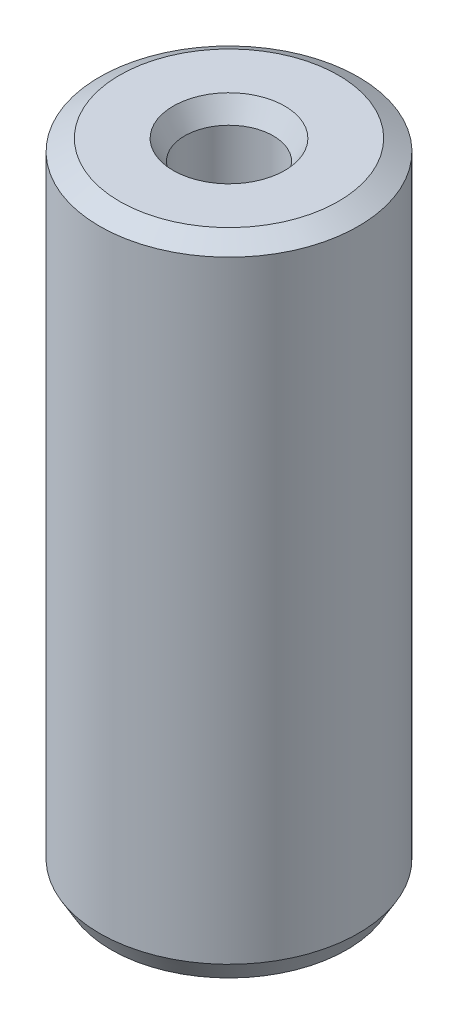
SolidWorks part; units mm, degrees
ref_plane "Front Plane" through (0, 0, 0) normal (0, 0, 1) x (1, 0, 0)
ref_plane "Top Plane" through (0, 0, 0) normal (0, 1, 0) x (1, 0, 0)
ref_plane "Right Plane" through (0, 0, 0) normal (1, 0, 0) x (0, 0, -1)
sketch "Sketch1" plane through (0, 0, 0) normal (0, 1, 0) x (1, 0, 0)
  circle A0 centre (0, 0) radius 5
  dimension "SLEEVE_OD" = 10
extrude "Boss-Extrude1" add sketch "Sketch1" along normal blind 24.8851
sketch "Sketch2" plane through (0, 0, 0) normal (0, 1, 0) x (1, 0, 0)
  circle A0 centre (0, 0) radius 1.7109
  dimension "BORE_D" = 3.4217
extrude "Cut-Extrude1" cut sketch "Sketch2" along normal through all
chamfer "Chamfer1" distance 0.4459 angle 60 4 edges at (0, 24.8851, 1.7109) (0, 0, 1.7109) (0, 0, 5) (0, 24.8851, 5) first distance on face at (0, 24.8851, 1.7109) first distance on face at (0, 0, 1.7109) first distance on face at (0, 24.8851, 5)
